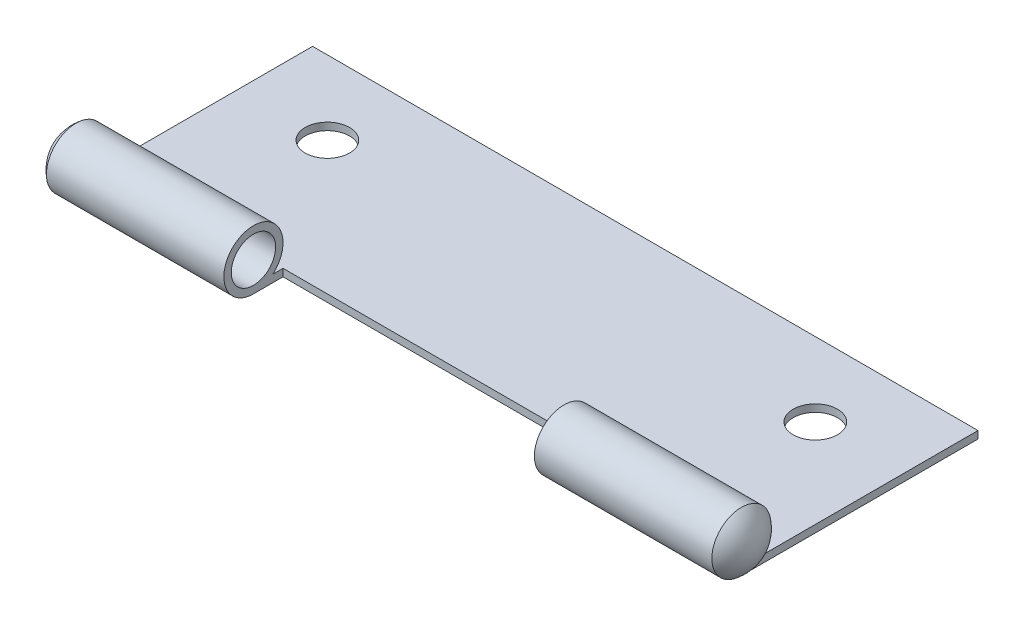
SolidWorks part; units mm, degrees
material "Latón"
ref_plane "Alzado" through (0, 0, 0) normal (0, 0, 1) x (1, 0, 0)
ref_plane "Planta" through (0, 0, 0) normal (0, 1, 0) x (1, 0, 0)
ref_plane "Vista lateral" through (0, 0, 0) normal (1, 0, 0) x (0, 0, -1)
sketch "Croquis1" plane through (0, 0, 0) normal (0, 1, 0) x (1, 0, 0)
  line L0 (22.5, 16) -> (22.5, 7.7131) construction
  line L1 (0, 0) -> (45, 0)
  line L2 (0, 0) -> (0, 16)
  line L3 (0, 16) -> (45, 16)
  line L4 (45, 0) -> (45, 16)
  circle A0 centre (6, 11) radius 1.5
  circle A1 centre (39, 11) radius 1.5
  dimension "D3" = 3
  dimension "D1" = 45
  dimension "D2" = 16
  dimension "D4" = 5
  dimension "D5" = 6
extrude "Saliente-Extruir1" add sketch "Croquis1" along normal blind 0.5
sketch "Croquis2" plane through (45, 0, 0) normal (1, 0, 0) x (0, 0, -1)
  circle A0 centre (0, 2) radius 2
  circle A1 centre (0, 2) radius 1.5
  dimension "D1" = 4
extrude "Saliente-Extruir2" add sketch "Croquis2" against normal up to surface (45 mm away) up to face at (0, 0.25, -8)
sketch "Croquis3" plane through (0, 0, 0) normal (0, -1, 0) x (1, 0, 0)
  line L0 (45, 2) -> (0, 2) construction
  line L1 (12, 2) -> (33, 2)
  line L2 (12, 2) -> (12, -2)
  line L3 (12, -2) -> (33, -2)
  line L4 (33, 2) -> (33, -2)
  line L5 (0, -2) -> (45, -2) construction
  line L6 (12, 0) -> (0, 0) construction
  line L7 (33, 0) -> (45, 0) construction
  line L8 (45, -2) -> (45, 2) construction
  dimension "D1" = 21
extrude "Cortar-Extruir1" cut sketch "Croquis3" against normal through all
sketch "Sketch1" plane through (0, 0, 0) normal (0, 0, 1) x (1, 0, 0)
  line L1 (0, 4) -> (0, 0) construction
  line L2 (0, 4) -> (0, 2)
  line L3 (-1, 2) -> (0, 2)
  line L4 (22.5, 0.5) -> (22.5, 8.4757) construction
  line L5 (12, 0.5) -> (33, 0.5) construction
  line L6 (-1, 2) -> (-1, 3.0576) construction
  line L7 (46, 2) -> (46, 3.0576) construction
  line L8 (0, 3.5) -> (0, 0.5) construction
  line L9 (46, 2) -> (45, 2)
  line L10 (45, 4) -> (45, 2)
  arc A0 (0, 4) -> (-1, 2) centre (1.5, 2) ccw
  arc A1 (45, 4) -> (46, 2) centre (43.5, 2) cw
  dimension "D1" = 1
revolve "Revolve2" add sketch "Sketch1" angle 360 about L3
